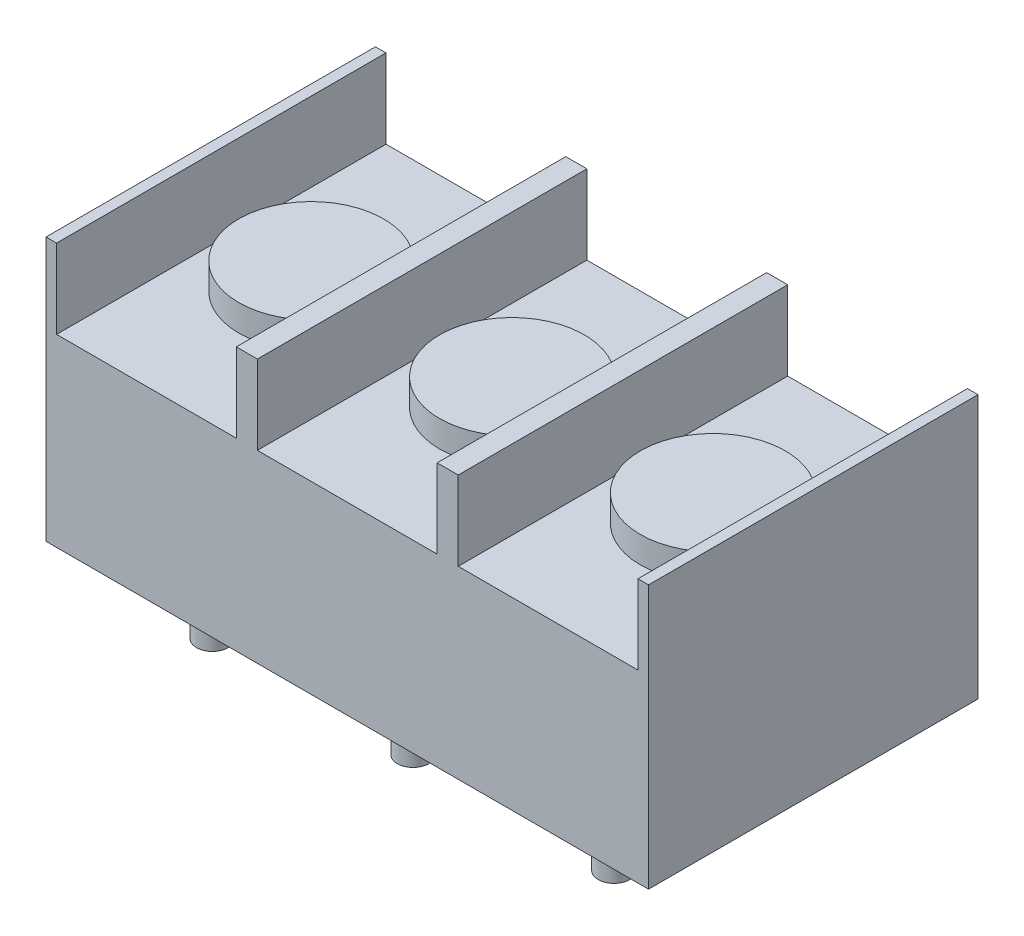
SolidWorks part; units mm, degrees
ref_plane "前视基准面" through (0, 0, 0) normal (0, 0, 1) x (1, 0, 0)
ref_plane "上视基准面" through (0, 0, 0) normal (0, 1, 0) x (1, 0, 0)
ref_plane "右视基准面" through (0, 0, 0) normal (1, 0, 0) x (0, 0, -1)
sketch "草图1" plane through (0, 0, 0) normal (0, 1, 0) x (1, 0, 0)
  line L0 (-11.1447, 0) -> (12.1543, 0) construction
  line L1 (-11.43, 6.25) -> (11.43, 6.25)
  line L2 (-11.43, 6.25) -> (-11.43, -6.25)
  line L3 (-11.43, -6.25) -> (11.43, -6.25)
  line L4 (11.43, 6.25) -> (11.43, -6.25)
  line L5 (0, 11.4931) -> (0, -8.9219) construction
  dimension "D1" = 22.86
  dimension "D2" = 12.5
extrude "拉伸1" add sketch "草图1" along normal blind 10
sketch "草图2" plane through (0, 10, 0) normal (0, 1, 0) x (-1, 0, 0)
  line L0 (0, 8.3959) -> (0, -7.6637) construction
  line L1 (11.43, 6.25) -> (-11.43, 6.25) construction
  line L2 (-11.03, 6.25) -> (-4.21, 6.25)
  line L3 (-11.03, 6.25) -> (-11.03, -6.25)
  line L4 (-11.03, -6.25) -> (-4.21, -6.25)
  line L5 (-4.21, 6.25) -> (-4.21, -6.25)
  line L6 (-11.43, -6.25) -> (11.43, -6.25) construction
  line L7 (-11.43, 6.25) -> (-11.43, -6.25) construction
  line L8 (-3.81, 8.3959) -> (-3.81, -7.4155) construction
  line L9 (-3.41, 6.25) -> (3.41, 6.25)
  line L10 (-3.41, 6.25) -> (-3.41, -6.25)
  line L11 (-3.41, -6.25) -> (3.41, -6.25)
  line L12 (3.41, 6.25) -> (3.41, -6.25)
  line L13 (4.21, 6.25) -> (11.03, 6.25)
  line L14 (4.21, 6.25) -> (4.21, -6.25)
  line L15 (4.21, -6.25) -> (11.03, -6.25)
  line L16 (11.03, 6.25) -> (11.03, -6.25)
  dimension "D1" = 0.4
  dimension "D2" = 3.81
  dimension "D3" = 0.4
extrude "切除-拉伸1" cut sketch "草图2" against normal blind 3
sketch "草图3" plane through (0, 0, 0) normal (0, -1, 0) x (1, 0, 0)
  line L0 (9.9189, 3.75) -> (-9.4712, 3.75) construction
  line L1 (0, -8.128) -> (0, 7.9902) construction
  circle A0 centre (0, 3.75) radius 0.6
  circle A1 centre (7.62, 3.75) radius 0.6
  circle A2 centre (-7.62, 3.75) radius 0.6
  dimension "D2" = 1.2
  dimension "D1" = 10
extrude "拉伸2" add sketch "草图3" along normal blind 2.54
sketch "草图4" plane through (0, 7, 0) normal (0, 1, 0) x (-1, 0, 0)
  circle A0 centre (0, 0) radius 2.75
  circle A1 centre (7.62, 0) radius 2.75
  circle A2 centre (-7.62, 0) radius 2.75
  dimension "D1" = 5.5
extrude "拉伸3" add sketch "草图4" along normal blind 1
